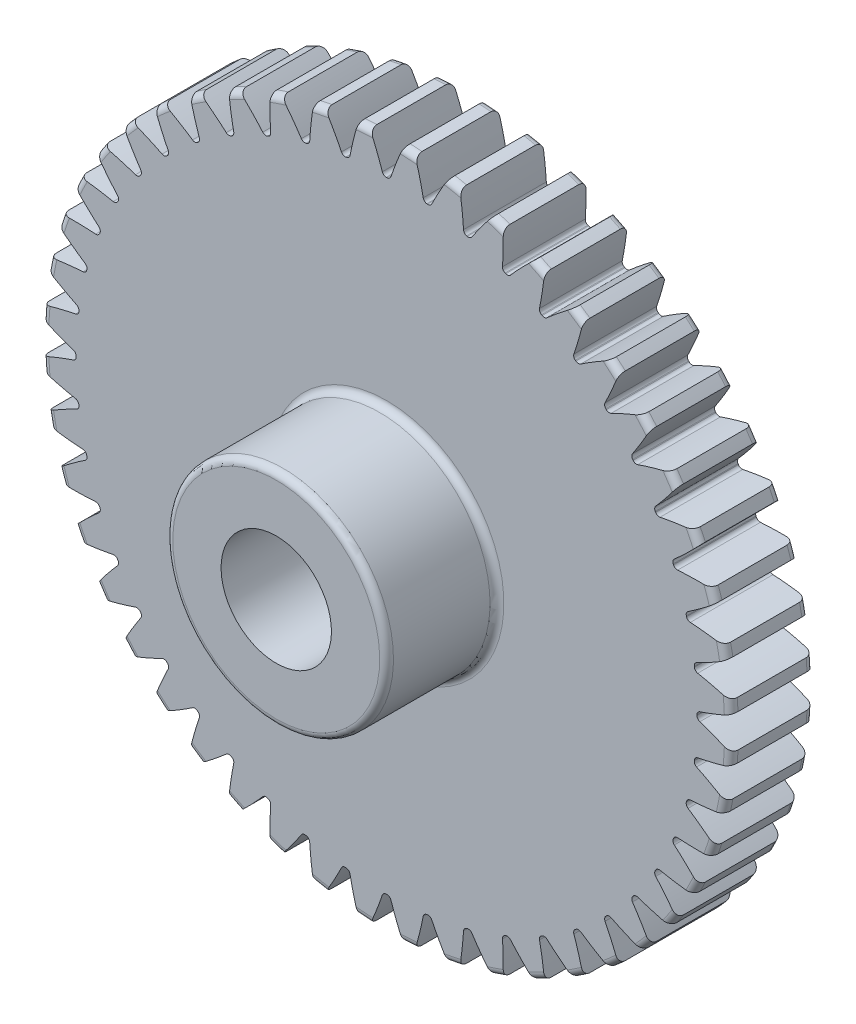
SolidWorks part; units mm, degrees
material "Delrin 2700 NC010, Low Viscosity Acetal Copolymer (SS)"
ref_plane "Front Plane" through (0, 0, 0) normal (0, 0, 1) x (1, 0, 0)
ref_plane "Top Plane" through (0, 0, 0) normal (0, 1, 0) x (1, 0, 0)
ref_plane "Right Plane" through (0, 0, 0) normal (1, 0, 0) x (0, 0, -1)
sketch "Sketch1" plane through (0, 0, 0) normal (0, 0, 1) x (1, 0, 0)
  line L0 (-609.6, 0) -> (609.6, 0) construction
  circle A0 centre (0, 0) radius 25 construction
  circle A1 centre (0, 0) radius 24 construction
  circle A2 centre (0, 0) radius 22.5 construction
  circle A3 centre (0, 0) radius 8 construction
  circle A4 centre (0, 0) radius 4 construction
  dimension "D2" = 1
  dimension "D3" = 2.5
  dimension "D1" = 2.5
sketch "Sketch2" plane through (0, 0, 0) normal (1, 0, 0) x (0, 0, -1)
  line L0 (0, 0) -> (-6, 0) construction
  line L1 (-6, 0) -> (-14, 0) construction
  dimension "Overall Width" = 14
  dimension "Face Width" = 6
sketch "Sketch4" plane through (0, 0, 0) normal (1, 0, 0) x (0, 0, -1)
  line L0 (-14, 4) -> (-14, 8)
  line L1 (-14, 8) -> (-6, 8)
  line L2 (-6, 8) -> (-6, 25)
  line L3 (-6, 25) -> (0, 25)
  line L4 (0, 25) -> (0, 4)
  line L5 (-6, 8) -> (-6, 0) construction
  line L6 (0, 25) -> (0, -25) construction
  line L7 (-6, 8) -> (0, 8) construction
  line L12 (-14, 4) -> (0, 4)
revolve "Revolve1" add sketch "Sketch4" angle 360 about L1
fillet "Fillet2" radius 0.5 4 edges at (0, 8, 14) (0, 8, 6) (0, 25, 6) (0, 25, 0)
sketch "Sketch7" plane through (0, 0, 6) normal (0, 0, 1) x (1, 0, 0)
  line L0 (0, 0) -> (0, 25) construction
  line L1 (0.7853, 23.9872) -> (1.1807, 24.9721) construction
  line L3 (1.6351, 24.9465) -> (1.5697, 23.9486) construction
  line L4 (1.5697, 23.9486) -> (1.4716, 22.4518) construction
  line L5 (0, 0) -> (1.4716, 22.4518) construction
  line L6 (0.7853, 23.9872) -> (0, 0) construction
  line L7 (0.7853, 23.9872) -> (0.818, 24.9866) construction
  line L8 (0.7853, 23.9872) -> (0, 0) construction
  circle A0 centre (0, 0) radius 25 construction
  arc A1 (-0.0275, 22.5) -> (0.0275, 22.5) centre (0, 0) cw
  circle A2 centre (0, 0) radius 22.5 construction
  arc A3 (-0.7853, 23.9872) -> (0.7853, 23.9872) centre (0, 0) cw construction
  circle A4 centre (0, 0) radius 24 construction
  arc A5 (2.0637, 24.9147) -> (1.2059, 24.9709) centre (0, 0) ccw construction
  arc A6 (0.7853, 23.9872) -> (2.3524, 23.8844) centre (0, 0) cw construction
  arc A7 (-1.2059, 24.9709) -> (1.2059, 24.9709) centre (0, 0) cw
  arc A8 (0.3122, 22.7043) -> (1.2059, 24.9709) centre (23.0572, 15.0452) cw
  arc A9 (-0.3122, 22.7043) -> (-1.2059, 24.9709) centre (-23.0572, 15.0452) ccw
  arc A10 (-0.0275, 22.5) -> (-0.3122, 22.7043) centre (-0.0278, 22.8) cw
  arc A11 (0.0275, 22.5) -> (0.3122, 22.7043) centre (0.0278, 22.8) ccw
  point P26 (-0.244, 22.4987)
  point P29 (0.244, 22.4987)
  dimension "D4" = 0.3
  dimension "D5" = 24
  dimension "D3" = 20
  dimension "D1" = 3.1416
  dimension "D2" = 1.5708
extrude "Cut-Extrude2" cut sketch "Sketch7" against normal through all
pattern_circular "CirPattern1" count 48 over 360 about axis through (0, 0, 14) along (0, 0, -1) of "Cut-Extrude2"
ref_axis "Axis1" through (0, 0, 14) along (0, 0, -1)
equation "\"D1@Sketch1\"=2.5*(\"Pitch Dia.@Sketch1\"/\"Number of Teeth@Sketch1\")"
equation "\"D1@CirPattern1\"=\"Number of Teeth@Sketch1\""
equation "\"D1@Fillet2\"=\"OD@Sketch1\"*.01"
equation "\"D1@Sketch7\"=3.14159*(\"Pitch Dia.@Sketch1\"/\"Number of Teeth@Sketch1\")"
equation "\"D2@Sketch7\"=\"D1@Sketch7\"/2"
equation "\"D4@Sketch7\"=\"D1@Sketch7\"*.0955"
equation "\"D5@Sketch7\"=\"Pitch Dia.@Sketch1\"/2"
